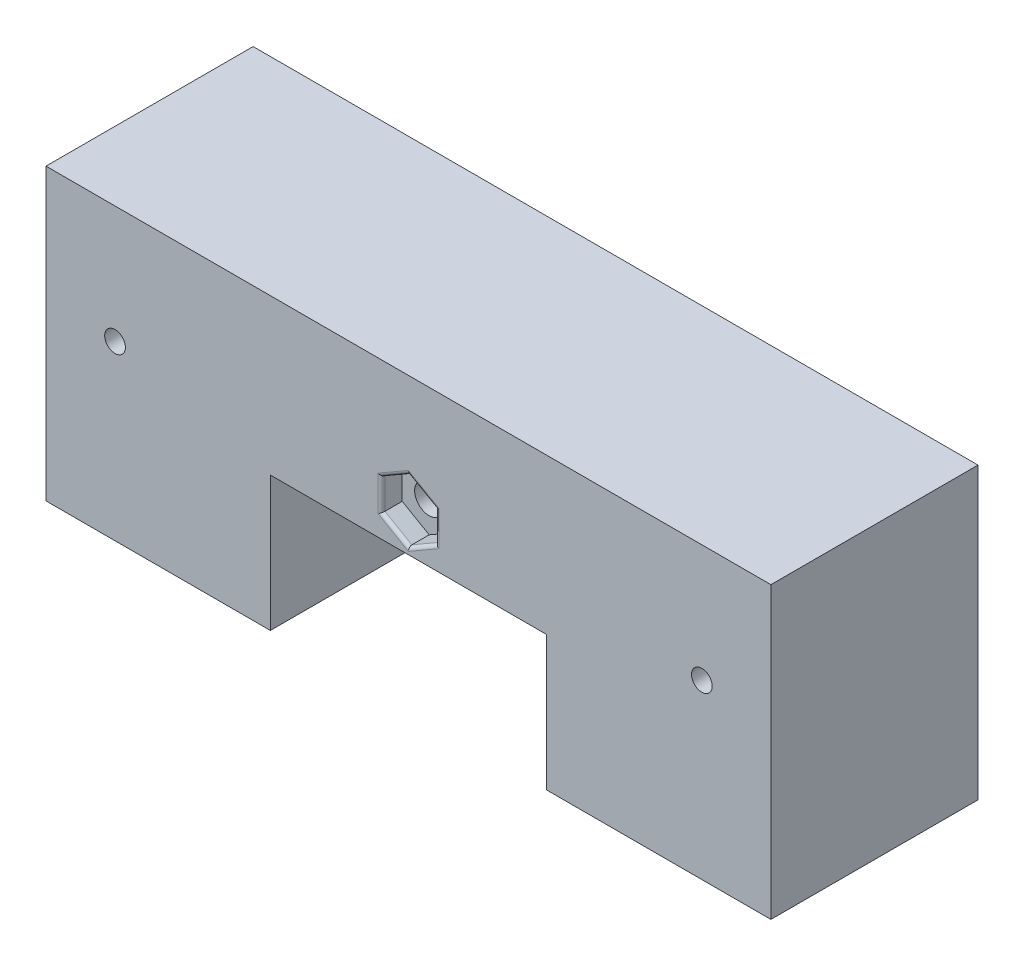
SolidWorks part; units mm, degrees
ref_plane "Plan de face" through (0, 0, 0) normal (0, 0, 1) x (1, 0, 0)
ref_plane "Plan de dessus" through (0, 0, 0) normal (0, 1, 0) x (1, 0, 0)
ref_plane "Plan de droite" through (0, 0, 0) normal (1, 0, 0) x (0, 0, -1)
sketch "Esquisse1" plane through (0, 0, 0) normal (0, 0, 1) x (1, 0, 0)
  line L1 (0, 0) -> (-105, 0)
  line L2 (0, 0) -> (0, 42)
  line L3 (0, 42) -> (-105, 42)
  line L4 (-105, 0) -> (-105, 42)
  dimension "D1" = 105
  dimension "D2" = 42
extrude "Boss.-Extru.1" add sketch "Esquisse1" along normal blind 30
sketch "Esquisse4" plane through (0, 0, 30) normal (0, 0, 1) x (1, 0, 0)
  line L0 (0, 42) -> (-105, 42) construction
  line L1 (-105, 42) -> (-105, 0) construction
  point P0 (-52.5, 42)
  point P1 (-105, 21)
sketch "Esquisse2" plane through (0, 0, 30) normal (0, 0, 1) x (1, 0, 0)
  line L0 (0, 0) -> (0, 42) construction
  line L1 (-52.5, 20.4967) -> (-48.6, 22.7483)
  line L2 (-48.6, 22.7483) -> (-48.6, 27.2517)
  line L3 (-48.6, 27.2517) -> (-52.5, 29.5033)
  line L4 (-52.5, 29.5033) -> (-56.4, 27.2517)
  line L5 (-56.4, 27.2517) -> (-56.4, 22.7483)
  line L6 (-56.4, 22.7483) -> (-52.5, 20.4967)
  circle A0 centre (-52.5, 25) radius 3.9 construction
  dimension "D1" = 7.8
  dimension "D2" = 17
extrude "Enlèv. mat.-Extru.1" cut sketch "Esquisse2" against normal blind 3
sketch "Esquisse3" plane through (0, 0, 30) normal (0, 0, 1) x (1, 0, 0)
  line L1 (-105, 42) -> (-105, 0) construction
  line L2 (0, 42) -> (-105, 42) construction
  circle A1 centre (-95, 25) radius 9.9745
  circle A3 centre (-95, 25) radius 1.5
  dimension "D5" = 3
  dimension "D3" = 10
  dimension "D7" = 17
fillet "Congé2" radius 0.5 6 edges at (-56.4, 25, 30) (-54.45, 21.6225, 30) (-50.55, 21.6225, 30) (-48.6, 25, 30) (-50.55, 28.3775, 30) (-54.45, 28.3775, 30)
sketch "Esquisse8" plane through (0, 0, 0) normal (0, 0, 1) x (1, 0, 0)
  line L0 (0, 0) -> (0, 42) construction
  circle A0 centre (-52.5, 25) radius 2.1038
  dimension "D1" = 17
  dimension "D2" = 52.5
extrude "Enlèv. mat.-Extru.3" cut sketch "Esquisse8" along normal through all
sketch "Esquisse10" plane through (0, 0, 0) normal (0, -1, 0) x (1, 0, 0)
  line L0 (-105, 30) -> (-105, 0) construction
  line L1 (-25, 10) -> (-5, 10)
  line L2 (-25, 10) -> (-25, 5)
  line L3 (-25, 5) -> (-5, 5)
  line L4 (-5, 10) -> (-5, 5)
  line L5 (-11.39, 27.5) -> (-6.39, 27.5)
  line L6 (-11.39, 27.5) -> (-11.39, 12.5)
  line L7 (-11.39, 12.5) -> (-6.39, 12.5)
  line L8 (-6.39, 27.5) -> (-6.39, 12.5)
  line L9 (-98.61, 27.5) -> (-93.61, 27.5)
  line L10 (-98.61, 27.5) -> (-98.61, 12.5)
  line L11 (-98.61, 12.5) -> (-93.61, 12.5)
  line L12 (-93.61, 27.5) -> (-93.61, 12.5)
  line L13 (-100, 10) -> (-80, 10)
  line L14 (-100, 10) -> (-100, 5)
  line L15 (-100, 5) -> (-80, 5)
  line L16 (-80, 10) -> (-80, 5)
  line L17 (0, 30) -> (0, 0) construction
  line L18 (-105, 0) -> (0, 0) construction
  dimension "D1" = 5
  dimension "D2" = 5
  dimension "D3" = 20
  dimension "D4" = 5
  dimension "D5" = 15
  dimension "D6" = 2.5
  dimension "D7" = 5
  dimension "D8" = 5
  dimension "D9" = 20
  dimension "D10" = 2.5
  dimension "D11" = 5
  dimension "D12" = 15
  dimension "D13" = 1.39
  dimension "D14" = 5
  dimension "D15" = 5
  dimension "D16" = 1.39
extrude "Enlèv. mat.-Extru.6" cut sketch "Esquisse10" against normal blind 8
extrude "Enlèv. mat.-Extru.7" cut sketch "Esquisse3" against normal through all contours A3
sketch "Esquisse14" plane through (0, 0, 30) normal (0, 0, 1) x (1, 0, 0)
  line L0 (0, 0) -> (0, 42) construction
  line L2 (0, 42) -> (-105, 42) construction
  circle A0 centre (-10, 25) radius 10
  circle A1 centre (-10, 25) radius 1.5
  dimension "D1" = 3
  dimension "D2" = 20
  dimension "D3" = 10
  dimension "D4" = 17
extrude "Enlèv. mat.-Extru.10" cut sketch "Esquisse14" against normal blind 30 contours A1
sketch "Esquisse15" plane through (0, 0, 30) normal (0, 0, 1) x (1, 0, 0)
  line L0 (-105, 0) -> (0, 0) construction
  line L1 (-72.5, 0) -> (-32.5, 0)
  line L2 (-72.5, 0) -> (-72.5, 19.5)
  line L3 (-72.5, 19.5) -> (-32.5, 19.5)
  line L4 (-32.5, 0) -> (-32.5, 19.5)
  line L5 (0, 0) -> (0, 42) construction
  dimension "D1" = 19.5
  dimension "D2" = 40
  dimension "D3" = 32.5
extrude "Enlèv. mat.-Extru.11" cut sketch "Esquisse15" against normal blind 20
sketch "Esquisse17" plane through (0, 19.5, 0) normal (0, -1, 0) x (-1, 0, 0)
  line L0 (32.5, -10) -> (32.5, -30) construction
  line L2 (32.5, -30) -> (72.5, -30) construction
  circle A0 centre (52.5, -20) radius 2
  point P4 (52.5, -30)
  dimension "D1" = 4
  dimension "D2" = 20
  dimension "D3" = 10
